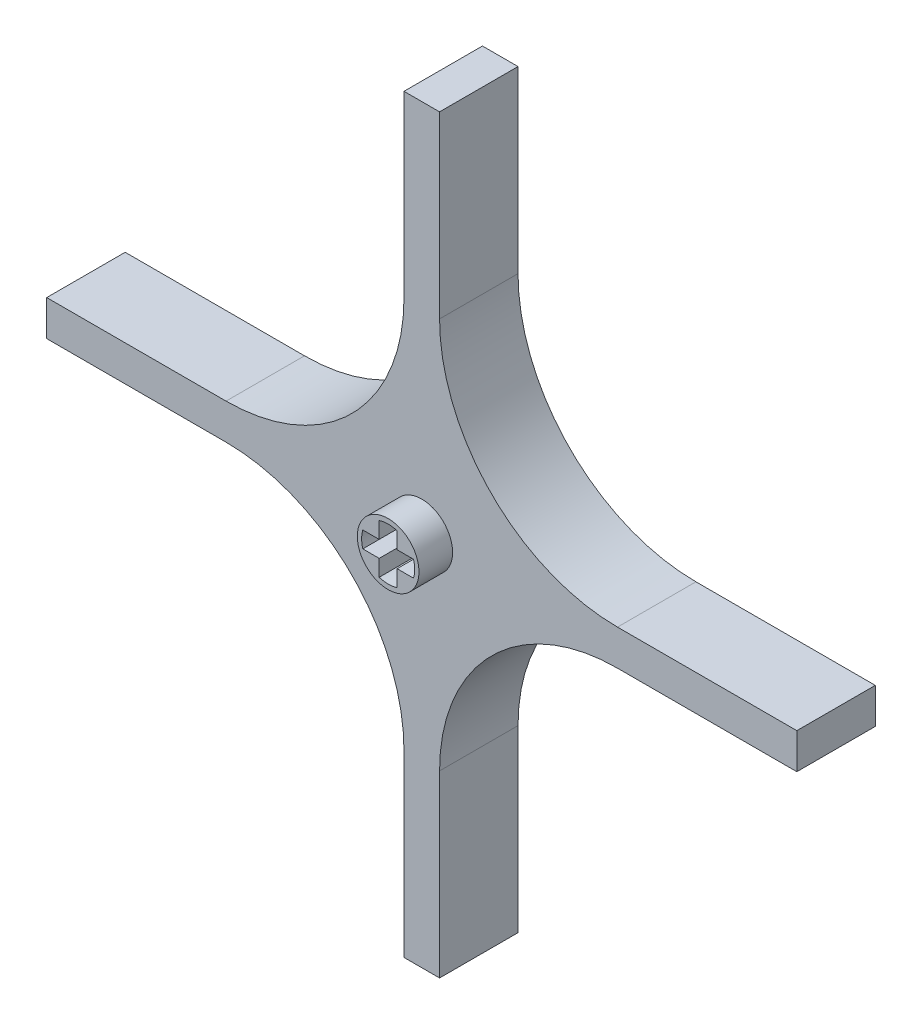
SolidWorks part; units mm, degrees
ref_plane "Front Plane" through (0, 0, 0) normal (0, 0, 1) x (1, 0, 0)
ref_plane "Top Plane" through (0, 0, 0) normal (0, 1, 0) x (1, 0, 0)
ref_plane "Right Plane" through (0, 0, 0) normal (1, 0, 0) x (0, 0, -1)
sketch "Sketch1" plane through (0, 0, 0) normal (0, 0, 1) x (1, 0, 0)
  line L0 (1.5875, -1.5875) -> (1.5875, -33.4645)
  line L1 (-1.5875, 33.4645) -> (1.5875, 33.4645)
  line L2 (-1.5875, 33.4645) -> (-1.5875, 1.5875)
  line L3 (-1.5875, -33.4645) -> (1.5875, -33.4645)
  line L4 (1.5875, 33.4645) -> (1.5875, 1.5875)
  line L5 (-1.5875, 33.4645) -> (1.5875, -33.4645) construction
  line L6 (-1.5875, -33.4645) -> (1.5875, 33.4645) construction
  line L7 (-33.4645, 1.5875) -> (-1.5875, 1.5875)
  line L8 (-33.4645, 1.5875) -> (-33.4645, -1.5875)
  line L9 (-33.4645, -1.5875) -> (-1.5875, -1.5875)
  line L10 (33.4645, 1.5875) -> (33.4645, -1.5875)
  line L11 (-33.4645, 1.5875) -> (33.4645, -1.5875) construction
  line L12 (-33.4645, -1.5875) -> (33.4645, 1.5875) construction
  line L13 (1.5875, -1.5875) -> (33.4645, -1.5875)
  line L14 (1.5875, 1.5875) -> (33.4645, 1.5875)
  line L15 (-1.5875, -1.5875) -> (-1.5875, -33.4645)
  circle A0 centre (17.526, 17.526) radius 15.9385 construction
  circle A1 centre (0, 0) radius 42.8625 construction
  point P0 (0, 0)
  point P6 (0, 0)
  dimension "D3" = 31.877
  dimension "D4" = 85.725
  dimension "D1" = 3.175
  dimension "D2" = 3.175
extrude "Boss-Extrude1" add sketch "Sketch1" along normal mid plane 7 contours L7 L2 L1 L4 L14 L10 L13 L0 L3 L15 L9 L8
fillet "Fillet1" radius 15.875 4 edges at (-1.5875, -1.5875, 0) (-1.5875, 1.5875, 0) (1.5875, -1.5875, 0) (1.5875, 1.5875, 0)
sketch "Sketch2" plane through (0, 0, 3.5) normal (0, 0, 1) x (1, 0, 0)
  circle A0 centre (0, 0) radius 42.8625
sketch "Sketch3" plane through (0, 0, -3.5) normal (0, 0, -1) x (-1, 0, 0)
  circle A0 centre (0, 0) radius 2.75
  dimension "D1" = 5.5
extrude "Boss-Extrude2" add sketch "Sketch3" along normal blind 3 and the other way blind 10
sketch "Sketch4" plane through (0, 0, -6.5) normal (0, 0, -1) x (-1, 0, 0)
  line L0 (-0.8, 0.7314) -> (-0.8, 2.1941)
  line L1 (0.8, 2.1941) -> (0.8, 0.7314)
  line L2 (-0.8, 0.7314) -> (0.8, 0.7314) construction
  line L3 (-0.8, 0.7314) -> (-0.8, -0.7314) construction
  line L4 (-0.8, 0.7314) -> (-2.2627, 0.7314)
  line L5 (-2.2627, -0.7314) -> (-0.8, -0.7314)
  line L6 (-0.8, -0.7314) -> (-0.8, -2.1941)
  line L7 (0.8, -2.1941) -> (0.8, -0.7314)
  line L8 (0.8, -0.7314) -> (2.2627, -0.7314)
  line L9 (0.8, 0.7314) -> (2.2627, 0.7314)
  line L10 (2.2627, 0.7314) -> (0.1891, 0.7314)
  circle A0 centre (0, 0) radius 2.5157 construction
  arc A1 (-0.8, 2.1941) -> (0.8, 2.1941) centre (0, -0.2798) cw
  arc A2 (-2.2627, 0.7314) -> (-2.2627, -0.7314) centre (0.2323, 0) ccw
  arc A3 (-0.8, -2.1941) -> (0.8, -2.1941) centre (0, 0.2798) ccw
  arc A4 (2.2627, 0.7314) -> (2.2627, -0.7314) centre (-0.2323, 0) cw
  point P6 (0, 0.7314)
  point P20 (-2.3677, 0)
  point P21 (0, -2.3202)
  point P22 (0, 0)
  dimension "D3" = 2.6
  dimension "D1" = 1.4627
  dimension "D2" = 1.6
extrude "Cut-Extrude1" cut sketch "Sketch4" against normal through all contours A4 L9 L1 A1 L0 L4 A2 L5 L6 A3 L7 L8 region at (0, 0, -6.5)
